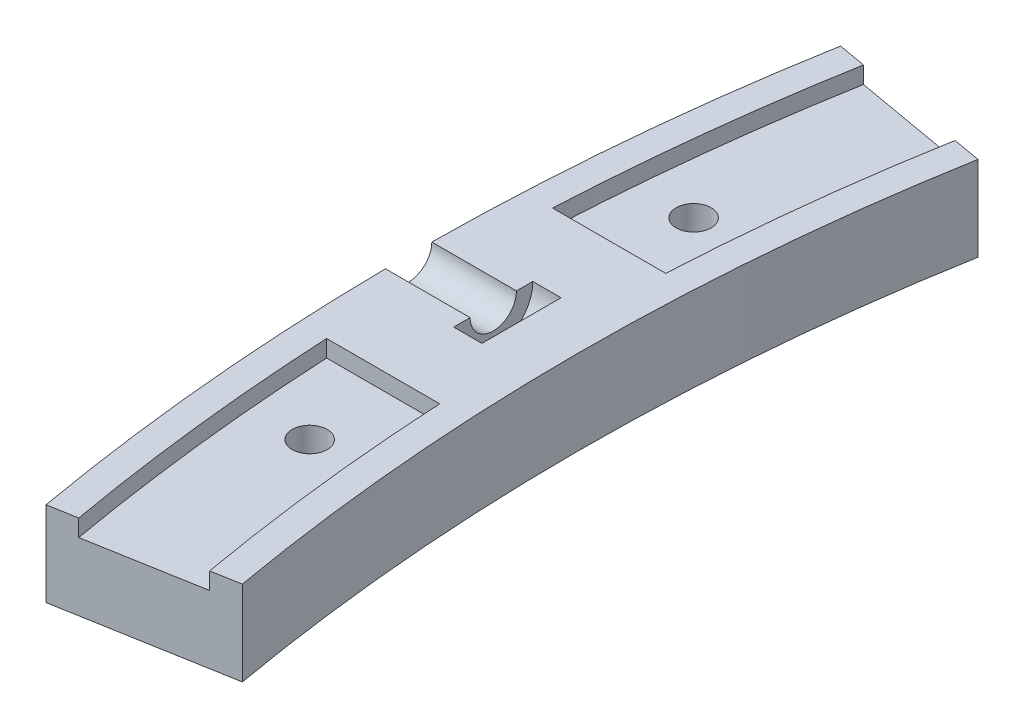
SolidWorks part; units mm, degrees
ref_plane "Front Plane" through (0, 0, 0) normal (0, 0, 1) x (1, 0, 0)
ref_plane "Top Plane" through (0, 0, 0) normal (0, 1, 0) x (1, 0, 0)
ref_plane "Right Plane" through (0, 0, 0) normal (1, 0, 0) x (0, 0, -1)
sketch "Sketch1" plane through (0, 0, 0) normal (0, 1, 0) x (1, 0, 0)
  line L0 (0, 0) -> (-199.4236, -35.1638) construction
  line L1 (0, 0) -> (-199.4236, 35.1638) construction
  line L2 (0, 0) -> (-195, 0) construction
  line L3 (-199.4236, 35.1638) -> (-184.6515, 32.559)
  line L4 (-184.6515, -32.559) -> (-199.4236, -35.1638)
  arc A0 (-196.9616, 34.7296) -> (-196.9616, -34.7296) centre (0, 0) ccw construction
  arc A1 (-187.1135, 32.9932) -> (-187.1135, -32.9932) centre (0, 0) ccw construction
  arc A2 (-192.0375, -33.8614) -> (-192.0375, 33.8614) centre (0, 0) cw construction
  arc A3 (-199.4236, 35.1638) -> (-199.4236, -35.1638) centre (0, 0) ccw
  arc A4 (-184.6515, 32.559) -> (-184.6515, -32.559) centre (0, 0) ccw
  dimension "D1" = 200
  dimension "D2" = 190
  dimension "D3" = 5
  dimension "D5" = 2.5
  dimension "D6" = 2.5
  dimension "D4" = 20
extrude "Boss-Extrude1" add sketch "Sketch1" along normal blind 7.5
sketch "Sketch2" plane through (0, 7.5, 0) normal (0, 1, 0) x (1, 0, 0)
  line L2 (0, 0) -> (-195, 0) construction
  line L3 (0, 0) -> (-199.4236, -35.1638) construction
  line L4 (0, 0) -> (-199.4236, 35.1638) construction
  line L5 (0, 0) -> (-190, 0) construction
  line L6 (0, 0) -> (-199.4236, -35.1638) construction
  line L7 (0, 0) -> (-199.4236, 35.1638) construction
  line L8 (0, 10) -> (-202.2529, 10) construction
  line L9 (0, 10) -> (0, -10) construction
  line L10 (0, -10) -> (-202.2529, -10) construction
  line L11 (-196.9616, 34.7296) -> (-187.1135, 32.9932)
  line L12 (-196.9616, -34.7296) -> (-187.1135, -32.9932)
  line L13 (-199.7498, -10) -> (-189.7367, -10)
  line L14 (-189.7367, 10) -> (-199.7498, 10)
  arc A0 (-196.9616, 34.7296) -> (-196.9616, -34.7296) centre (0, 0) ccw construction
  arc A1 (-187.1135, 32.9932) -> (-187.1135, -32.9932) centre (0, 0) ccw construction
  arc A2 (-196.9616, 34.7296) -> (-196.9616, -34.7296) centre (0, 0) ccw
  arc A3 (-187.1135, 32.9932) -> (-187.1135, -32.9932) centre (0, 0) ccw
  arc A4 (-199.4236, 35.1638) -> (-199.4236, -35.1638) centre (0, 0) ccw construction
  line M2 (-199.4236, -35.1638) -> (-184.6515, -32.559)
  line M4 (-184.6515, 32.559) -> (-199.4236, 35.1638)
  dimension "D1" = 20
extrude "Cut-Extrude1" cut sketch "Sketch2" against normal blind 1.5 contours A3 A2 L14 M4 | A3 L13 A2 M2 region at (-193.6958, 7.5, -21.9638) region at (-193.6958, 7.5, 21.9638)
ref_plane "Plane1" through (-195, 0, 0) normal (1, 0, 0) x (0, 0, -1)
sketch "Sketch4" plane through (-195, 0, 0) normal (1, 0, 0) x (0, 0, -1)
  line L0 (32.559, 7.5) -> (-32.559, 7.5) construction
  circle A0 centre (0, 7.5) radius 3.5
  dimension "D1" = 7
extrude "Cut-Extrude3" cut sketch "Sketch4" along normal blind 2.5
sketch "Sketch5" plane through (-195, 0, 0) normal (1, 0, 0) x (0, 0, -1)
  line L0 (32.559, 7.5) -> (-32.559, 7.5) construction
  circle A0 centre (0, 7.5) radius 2.05
  dimension "D1" = 4.1
extrude "Cut-Extrude4" cut sketch "Sketch5" against normal through all
sketch "Sketch6" plane through (0, 0, 0) normal (0, -1, 0) x (1, 0, 0)
  line L0 (0, 0) -> (-194.258, 16.9954) construction
  line L1 (0, 0) -> (-195, 0) construction
  line L2 (0, 0) -> (-195, 0) construction
  line L3 (0, 0) -> (-194.258, -16.9954) construction
  arc A0 (-192.0375, 33.8614) -> (-192.0375, -33.8614) centre (0, 0) ccw construction
  dimension "D1" = 5
hole_wizard "Ø3.1 (3.1) Diameter Hole1" positions "Sketch7" profile "Sketch8" hole size "Ø3.1" standard "ISO" end condition through all
sketch "Sketch7" plane through (0, 0, 0) normal (0, -1, 0) x (-1, 0, 0)
  point P0 (194.258, -16.9954)
  point P3 (194.258, 16.9954)
sketch "Sketch8" plane through (-194.258, 0, 16.9954) normal (1, 0, 0) x (0, 0, -1)
  line L0 (0, 0) -> (0, 7.6156)
  line L1 (0, 7.6156) -> (1.55, 7.6156)
  line L2 (1.55, 7.6156) -> (1.55, 0)
  line L5 (1.55, 0) -> (0, 0)
  line L11 (0, -6.35) -> (0, 107.95) construction
  dimension "Thru Hole Dia." = 3.1
  dimension "Thru Hole Depth" = 7.6156
